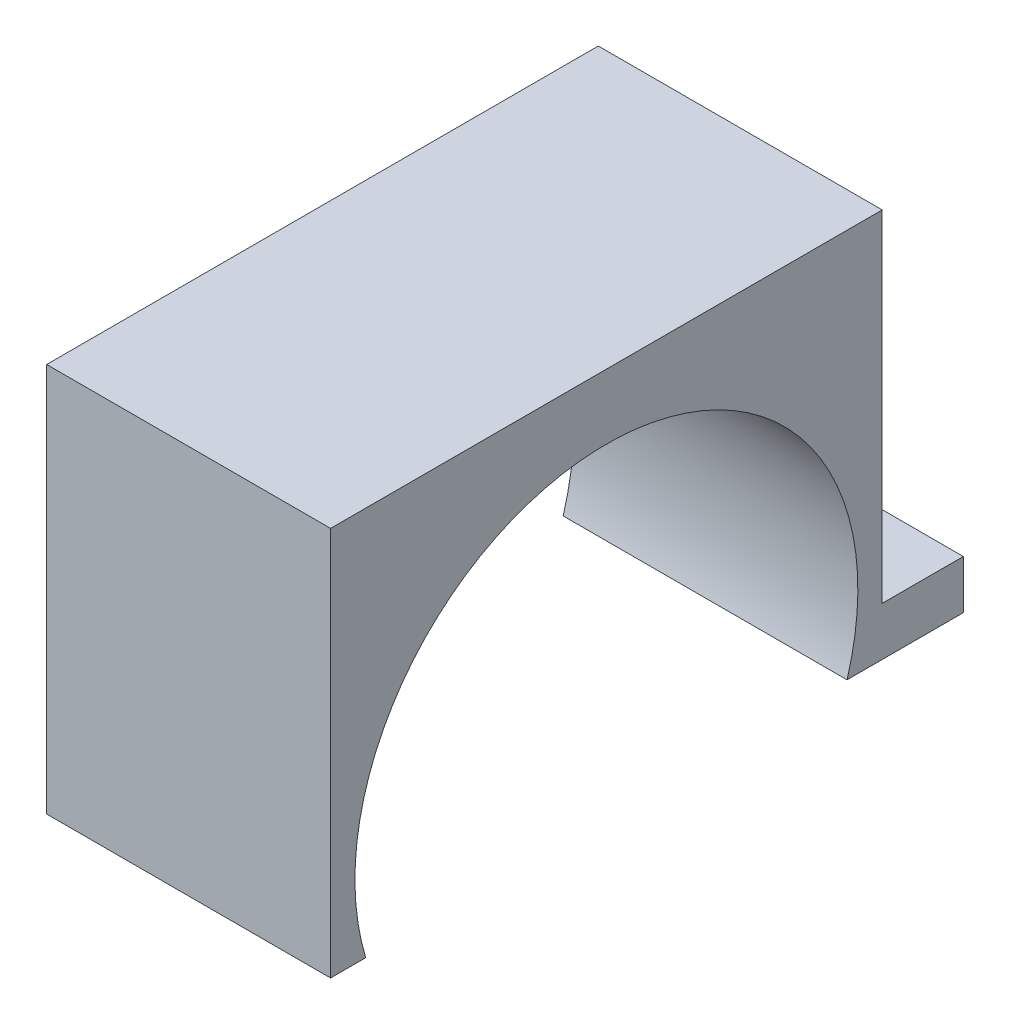
SolidWorks part; units mm, degrees
ref_plane "前视基准面" through (0, 0, 0) normal (0, 0, 1) x (1, 0, 0)
ref_plane "上视基准面" through (0, 0, 0) normal (0, 1, 0) x (1, 0, 0)
ref_plane "右视基准面" through (0, 0, 0) normal (1, 0, 0) x (0, 0, -1)
sketch "草图1" plane through (0, 0, 0) normal (0, 1, 0) x (1, 0, 0)
  line L1 (0, 0) -> (17, 0)
  line L2 (0, 0) -> (0, -40)
  line L3 (0, -40) -> (17, -40)
  line L4 (17, 0) -> (17, -40)
  dimension "D1" = 17
  dimension "D2" = 40
extrude "凸台-拉伸1" add sketch "草图1" along normal blind 50
sketch "草图2" plane through (0, 0, 0) normal (0, -1, 0) x (1, 0, 0)
  line L0 (0, 39) -> (0, 40)
  line L1 (-0.5, 39) -> (17, 39) construction
  line L2 (0, 0) -> (0, 40) construction
  line L3 (0, 40) -> (17, 40)
  line L4 (17, 40) -> (17, 39)
  line L5 (17, 40) -> (17, 0) construction
  line L6 (17, 39) -> (0, 39)
extrude "切除-拉伸1" cut sketch "草图2" against normal through all
sketch "草图4" plane through (0, 0, 0) normal (0, -1, 0) x (1, 0, 0)
  line L2 (-0.5, 0) -> (0, 0)
  line L3 (0, 0) -> (0, 39)
  line L4 (-0.5, 0) -> (-0.5, 39)
  line L5 (-0.5, 39) -> (0, 39)
extrude "凸台-拉伸2" add sketch "草图4" against normal up to vertex (50 mm away) up to point (0, 50, 39)
sketch "草图5" plane through (17, 0, 0) normal (1, 0, 0) x (0, 0, -1)
  circle A0 centre (-22, 4.5) radius 15.5
extrude "切除-拉伸2" cut sketch "草图5" against normal up to vertex (17.5 mm away) up to point (-0.5, 0, 0)
sketch "草图6" plane through (17, 0, 0) normal (1, 0, 0) x (0, 0, -1)
  line L0 (0, 24) -> (0, 3)
  line L2 (-22, 24) -> (-5, 24)
  line L3 (0, 50) -> (0, 0) construction
  line L4 (0, 24) -> (0, 50)
  line L5 (0, 50) -> (-39, 50)
  line L6 (-39, 50) -> (-39, 24)
  line L7 (-39, 50) -> (-39, 0) construction
  line L8 (-39, 24) -> (-22, 24)
  line L9 (0, 0) -> (0, 3)
  line L10 (0, 3) -> (-5, 3)
  line L11 (-5, 3) -> (-5, 24)
  line L12 (0, 24) -> (0, 3)
  line M11 (0, 0) -> (0, 50)
  line M12 (0, 50) -> (-39, 50)
  line M13 (-39, 50) -> (-39, 0)
extrude "切除-拉伸3" cut sketch "草图6" against normal up to vertex (17.5 mm away) contours L11 L10 L8 L2 M11 M12 M13 region at (17, 34.7949, 17.9048) up to point (-0.5, 0, 0)
sketch "草图7" plane through (0, 3, 0) normal (0, 1, 0) x (1, 0, 0)
  line L0 (8.25, -5) -> (8.25, 0)
  line L1 (-0.5, -5) -> (17, -5) construction
  line L2 (-0.5, 0) -> (17, 0) construction
  circle A0 centre (8.25, -2.5) radius 1.6
extrude "切除-拉伸4" cut sketch "草图7" against normal up to vertex (3 mm away) contours L0 A0 | L0 A0 region at (7.5709, 3, 2.5) region at (8.9291, 3, 2.5) up to point (17, 0, 0)
